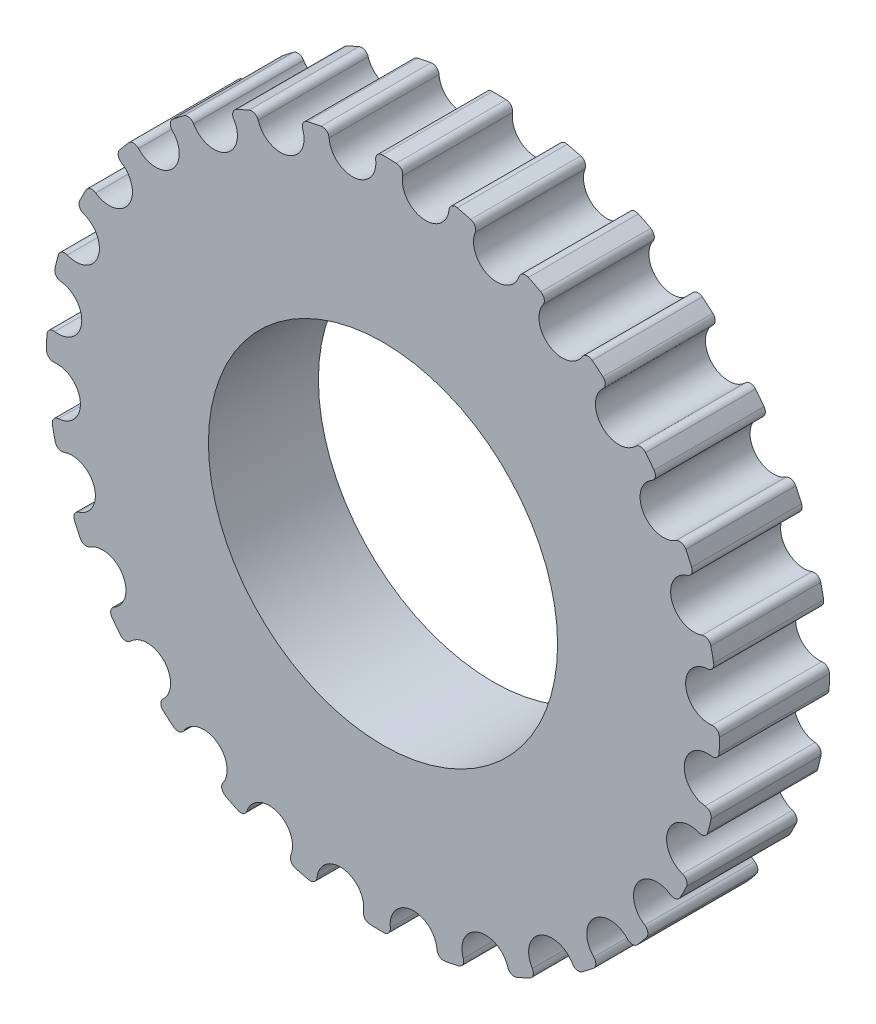
SolidWorks part; units mm, degrees
ref_plane "Front Plane" through (0, 0, 0) normal (0, 0, 1) x (1, 0, 0)
ref_plane "Top Plane" through (0, 0, 0) normal (0, 1, 0) x (1, 0, 0)
ref_plane "Right Plane" through (0, 0, 0) normal (1, 0, 0) x (0, 0, -1)
sketch "PD" plane through (0, 0, 0) normal (0, 0, 1) x (1, 0, 0)
  circle A0 centre (0, 0) radius 22.2817
  circle A1 centre (0, 0) radius 11.1125
  dimension "PD" = 44.5634
  dimension "D1" = 22.225
extrude "half width" add sketch "PD" along normal blind 7
sketch "Sketch3" plane through (0, 0, 7) normal (0, 0, 1) x (1, 0, 0)
  line L0 (0, 0) -> (0, 21.4117) construction
  line L2 (0, 0) -> (2.7204, 20.6634) construction
  line L3 (0, 21.4117) -> (0, 22.2817)
  line L4 (5.5418, 20.6821) -> (5.7669, 21.5225)
  line L6 (2.7204, 20.6634) -> (2.9083, 22.0911) construction
  arc A0 (0.8412, 21.3952) -> (1.2489, 20.8978) centre (0.8243, 20.9655) cw
  arc A1 (1.2489, 20.8978) -> (4.2024, 20.509) centre (2.7204, 20.6634) ccw
  circle A2 centre (0, 0) radius 22.2817 construction
  arc A3 (0, 22.2817) -> (5.7669, 21.5225) centre (0, 0) cw
  arc A4 (4.7249, 20.8839) -> (4.2024, 20.509) centre (4.6301, 20.4645) ccw
  arc A5 (0.8412, 21.3952) -> (0, 21.4117) centre (0, 0) ccw
  arc A6 (5.5418, 20.6821) -> (4.7249, 20.8839) centre (0, 0) ccw
  point P8 (2.5259, 19.1861)
  dimension "D1" = 0.43
  dimension "D2" = 1.49
  dimension "D5" = 2.93
  dimension "D3" = 0.87
  dimension "D4" = 7.5
extrude "Teeth " cut sketch "Sketch3" against normal up to surface (7 mm away) up to face at (22.2817, 0, 0)
pattern_circular "CirPattern1" count 28 over 360 about axis through (0, 0, 7) along (0, 0, 1) of "Teeth "
equation "\"n\"= 28"
equation "\"p\"= 5'pitch"
equation "\"pd\"= \"n\" * \"p\" / pi'pitch diameter"
equation "\"PD@PD\"=\"pd\""
equation "\"D1@CirPattern1\"=\"n\""
equation "\"Bolt diameter\"= 3mm"
